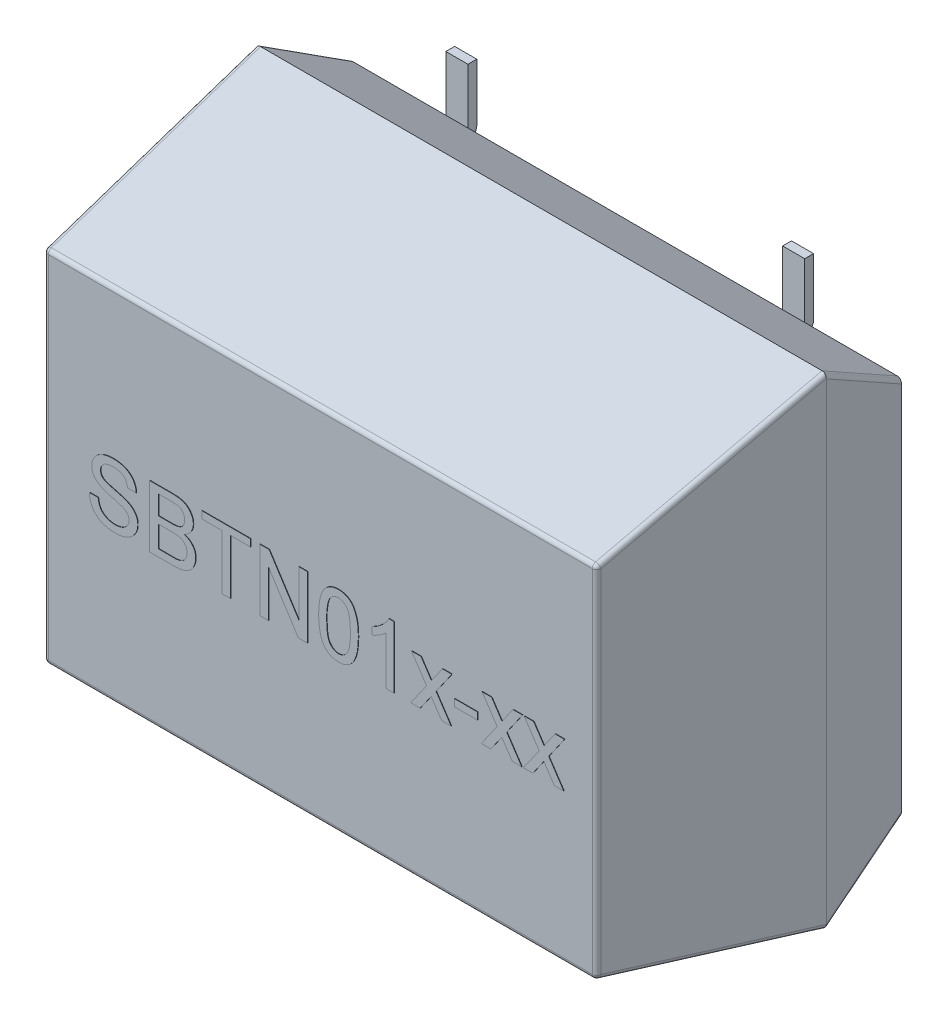
SolidWorks part; units mm, degrees
ref_plane "Спереди" through (0, 0, 0) normal (0, 0, 1) x (1, 0, 0)
ref_plane "Сверху" through (0, 0, 0) normal (0, 1, 0) x (1, 0, 0)
ref_plane "Справа" through (0, 0, 0) normal (1, 0, 0) x (0, 0, -1)
sketch "Эскиз1" plane through (0, 0, 0) normal (1, 0, 0) x (0, 0, -1)
  line L0 (-0.2, -4.3) -> (-0.2, 4.3)
  line L1 (-0.2, 4.3) -> (-2.1, 5.45)
  line L2 (-2.1, 5.45) -> (-7.1, 4.05)
  line L3 (-7.1, 4.05) -> (-7.1, -4.05)
  line L4 (-7.1, -4.05) -> (-2.1, -5.45)
  line L5 (-2.1, -5.45) -> (-0.2, -4.3)
  line L6 (-2.1, -5.45) -> (-2.1, 5.45) construction
  line L7 (0, 0) -> (-7.1, 0) construction
  point P6 (-2.6438, 4.8852)
  point P8 (-2.5393, -4.7748)
  point P11 (-2.7496, 4.702)
  point P12 (-2.157, -5.6121)
  point P13 (-2.1, 0)
  point P14 (-2.2791, 4.9015)
  point P15 (-0.2, 0)
  point P16 (-0.3995, 2.8826)
  dimension "D1" = 7.1
  dimension "D2" = 10.9
  dimension "D3" = 8.1
  dimension "D4" = 5
  dimension "D5" = 8.6
  dimension "D7" = 6.9
extrude "Бобышка-Вытянуть1" add sketch "Эскиз1" along normal mid plane 12.9
sketch "Эскиз2" plane through (0, 0, 0) normal (0, 1, 0) x (1, 0, 0)
  line L0 (-6.45, -2.1) -> (-6.25, -7.1)
  line L1 (-6.25, -7.1) -> (6.25, -7.1)
  line L2 (6.25, -7.1) -> (6.45, -2.1)
  line L3 (6.45, -2.1) -> (6.25, -0.2)
  line L4 (6.25, -0.2) -> (-6.25, -0.2)
  line L5 (-6.25, -0.2) -> (-6.45, -2.1)
  line L6 (6.45, -0.2) -> (-6.45, -0.2) construction
  line L7 (6.45, -7.1) -> (-6.45, -7.1) construction
  line L8 (-6.45, -2.1) -> (-6.45, -0.2) construction
  line L9 (6.45, -2.1) -> (6.45, -0.2) construction
  line L10 (0, 0) -> (0, -7.1) construction
  line L11 (6.45, -2.1) -> (-6.45, -2.1) construction
  point P10 (4.3143, -0.2)
  point P18 (0, -0.2)
  point P19 (0, 0)
  point P21 (-5.8073, -4.8768)
  point P23 (0, 0)
  dimension "D1" = 0.2
  dimension "D2" = 0.2
extrude "Вырез-Вытянуть1" cut sketch "Эскиз2" against normal through all both and the other way through all flip side to cut
fillet "Скругление1" radius 0.1 12 edges at (6.35, 4.875, 1.15) (-6.35, 4.875, 1.15) (-6.35, -4.75, 4.6) (-6.35, 4.75, 4.6) (6.35, -4.875, 1.15) (-6.35, -4.875, 1.15) (6.35, -4.75, 4.6) (6.35, 4.75, 4.6) (0, -4.05, 7.1) (-6.25, 0, 7.1) (0, 4.05, 7.1) (6.25, 0, 7.1)
ref_plane "Плоскость1" through (-3.81, 0, 0) normal (1, 0, 0) x (0, 0, -1)
sketch "Эскиз3" plane through (-3.81, 0, 0) normal (1, 0, 0) x (0, 0, -1)
  line L0 (0, -5.55) -> (0, -4.25)
  line L2 (-0.2, -4.05) -> (-0.2, -5.55)
  line L3 (-0.2, -5.55) -> (0, -5.55)
  line L4 (-0.2, -4.1894) -> (-0.2, 4.1894) construction
  line L5 (0, 4.25) -> (0, 5.55)
  line L6 (0, 5.55) -> (-0.2, 5.55)
  line L7 (-0.2, 5.55) -> (-0.2, 4.05)
  line L8 (0, 5.55) -> (0, -5.55) construction
  arc A0 (0, -4.25) -> (-0.2, -4.05) centre (-0.2, -4.25) ccw
  arc A2 (0, 4.25) -> (-0.2, 4.05) centre (-0.2, 4.25) cw
  point P15 (-0.2, -4.3)
  dimension "D1" = 11.1
  dimension "D2" = 0.25
extrude "Бобышка-Вытянуть2" add sketch "Эскиз3" along normal mid plane 0.5
mirror "Зеркальное отражение1" about plane through (0, 0, 0) normal (1, 0, 0) of "Бобышка-Вытянуть2"
pattern_linear "Линейный массив1" count 2 spacing 2.54 along (1, 0, 0) of face at (-3.81, -4.925, 0.2) of face at (-4.06, -4.7317, 0.1117) of face at (-3.81, -5.55, 0.1) of face at (-3.81, -4.9, 0) of face at (-3.56, -4.7317, 0.1117) of face at (-3.81, -4.1293, 0.0793)
sketch "Эскиз4" plane through (0, 0, 7.1) normal (0, 0, 1) x (1, 0, 0)
  text T0 "SBTN01x-xx" font "Arial" height 1.4
  point P1 (-5.0278, -0.8144)
  point P2 (0, 0)
extrude "Бобышка-Вытянуть3" add sketch "Эскиз4" along normal blind 0.01
